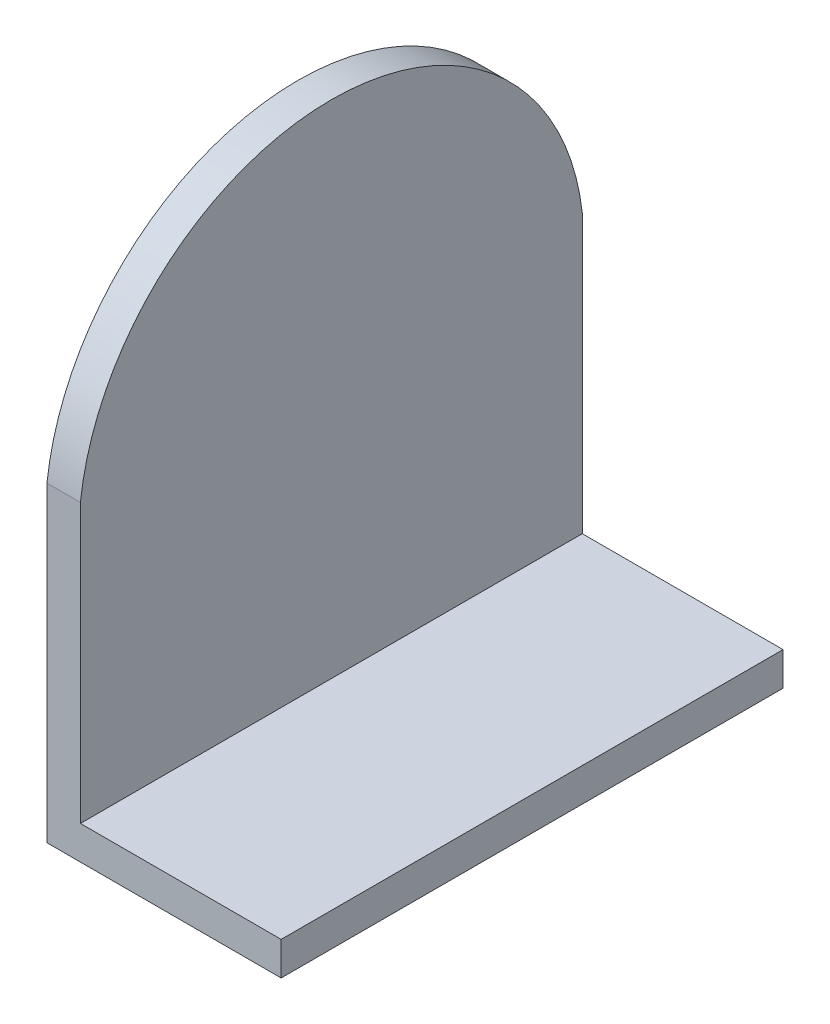
SolidWorks part; units mm, degrees
ref_plane "Спереди" through (0, 0, 0) normal (0, 0, 1) x (1, 0, 0)
ref_plane "Сверху" through (0, 0, 0) normal (0, 1, 0) x (1, 0, 0)
ref_plane "Справа" through (0, 0, 0) normal (1, 0, 0) x (0, 0, -1)
sketch "Эскиз1" plane through (0, 0, 0) normal (0, 0, 1) x (1, 0, 0)
  line L0 (0, 0) -> (0, 30)
  line L1 (0, 0) -> (12, 0)
extrude "Вытянуть-Тонкостенный1" add sketch "Эскиз1" along normal blind 30 thin thin type one direction wall 2
sketch "Эскиз2" plane through (-2, 0, 0) normal (-1, 0, 0) x (0, 0, 1)
  line L0 (-0.0987, 15.1811) -> (-3.6788, 15.1811)
  line L1 (-3.6788, 15.1811) -> (-3.6788, 31.571)
  line L2 (-3.6788, 31.571) -> (33.6004, 31.571)
  line L5 (33.6004, 31.571) -> (33.6004, 15.1811)
  line L6 (33.6004, 15.1811) -> (30.0987, 15.1811)
  arc A0 (30.0987, 15.1811) -> (-0.0987, 15.1811) centre (15, 14.8646) ccw
extrude "Вытянуть1" cut sketch "Эскиз2" against normal through all
